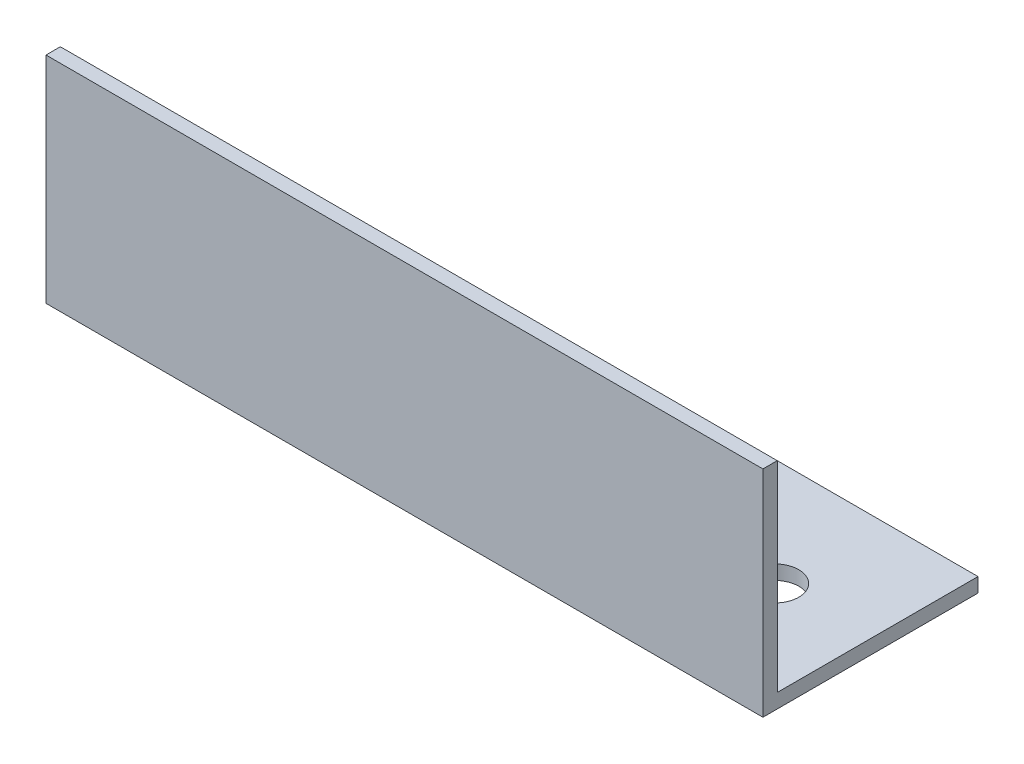
SolidWorks part; units mm, degrees
ref_plane "Спереди" through (0, 0, 0) normal (0, 0, 1) x (1, 0, 0)
ref_plane "Сверху" through (0, 0, 0) normal (0, 1, 0) x (1, 0, 0)
ref_plane "Справа" through (0, 0, 0) normal (1, 0, 0) x (0, 0, -1)
sketch "Эскиз1" plane through (0, 0, 0) normal (1, 0, 0) x (0, 0, -1)
  line L0 (0, 0) -> (0, 45)
  line L1 (0, 0) -> (45, 0)
  dimension "D1" = 45
extrude "Вытянуть-Тонкостенный1" add sketch "Эскиз1" along normal blind 150 thin thin type one direction reverse wall 3
sketch "Эскиз2" plane through (0, 0, 0) normal (0, -1, 0) x (1, 0, 0)
  line L0 (150, -45) -> (0, -45) construction
  line L1 (0, 0) -> (0, -45) construction
  circle A0 centre (30, -22.5) radius 5
  circle A1 centre (130, -22.5) radius 5
  dimension "D1" = 22.5
  dimension "D3" = 10
  dimension "D2" = 30
  dimension "D4" = 2
extrude "Вырез-Вытянуть1" cut sketch "Эскиз2" against normal through all
